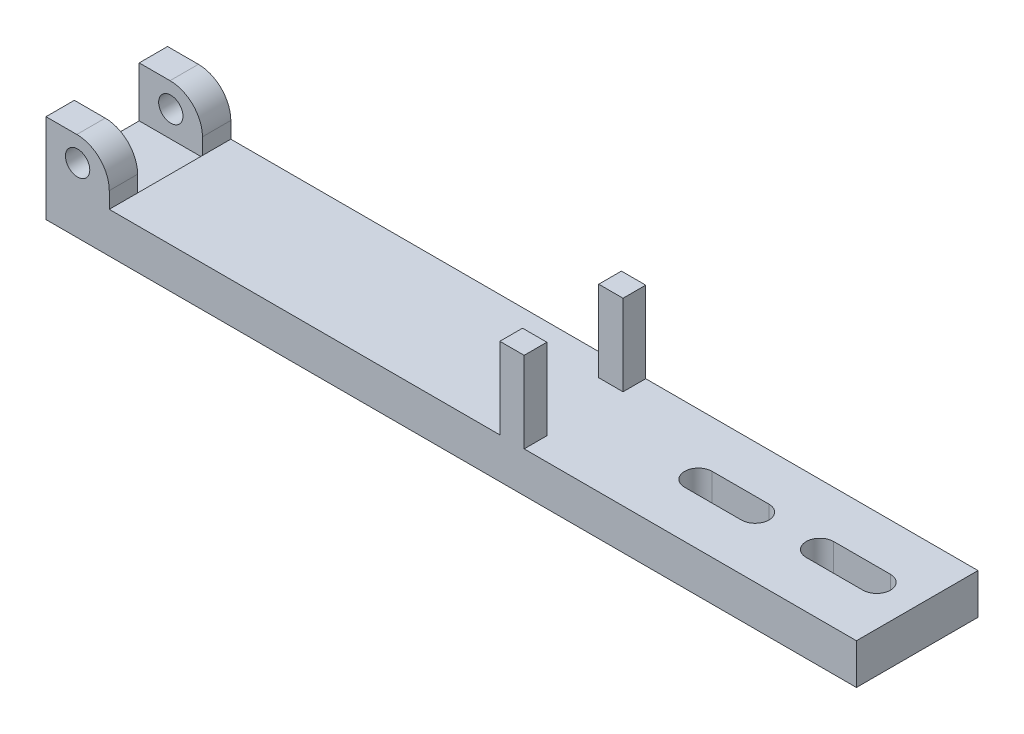
SolidWorks part; units mm, degrees
ref_plane "Ebene vorne" through (0, 0, 0) normal (0, 0, 1) x (1, 0, 0)
ref_plane "Ebene oben" through (0, 0, 0) normal (0, 1, 0) x (1, 0, 0)
ref_plane "Ebene rechts" through (0, 0, 0) normal (1, 0, 0) x (0, 0, -1)
sketch "Sketch1" plane through (0, 0, 0) normal (0, 1, 0) x (1, 0, 0)
  line L0 (-50, -7.5) -> (-50, 7.5)
  line L1 (-50, -7.5) -> (50, -7.5)
  line L2 (-50, 7.5) -> (50, 7.5)
  line L3 (50, -7.5) -> (50, 7.5)
  line L4 (-50, -7.5) -> (50, 7.5) construction
  line L5 (-50, 7.5) -> (50, -7.5) construction
  point P1 (0, 0)
  dimension "D1" = 15
  dimension "D2" = 100
extrude "Boss-Extrude1" add sketch "Sketch1" along normal blind 5
sketch "Sketch2" plane through (0, 5, 0) normal (0, 1, 0) x (1, 0, 0)
  line L0 (-50, -7.5) -> (50, -7.5) construction
  line L1 (-50, 7.5) -> (-42.1952, 7.5)
  line L2 (-50, 7.5) -> (-50, -7.5)
  line L3 (-50, -7.5) -> (-42.1952, -7.5)
  line L4 (-42.1952, 7.5) -> (-42.1952, -7.5)
extrude "Boss-Extrude2" add sketch "Sketch2" along normal blind 6
sketch "Sketch3" plane through (0, 0, 7.5) normal (0, 0, 1) x (1, 0, 0)
  line L1 (-42.1952, 8) -> (-50, 8) construction
  line L2 (-42.1952, 11) -> (-42.1952, 5) construction
  line L3 (-50, 11) -> (-50, 0) construction
  circle A0 centre (-46.0976, 8) radius 1.5
  dimension "D1" = 3
extrude "Cut-Extrude1" cut sketch "Sketch3" against normal up to surface (15 mm away) up to face at (-14.0651, 5.3333, -7.5)
fillet "Fillet1" radius 4 1 edges at (-42.1952, 11, 0)
sketch "Sketch4" plane through (0, 11, 0) normal (0, 1, 0) x (1, 0, 0)
  line L0 (-42.1952, 0) -> (-50, 0) construction
  line L1 (-42.1952, -7.5) -> (-42.1952, 7.5) construction
  line L2 (-50, 7.5) -> (-50, -7.5) construction
  line L3 (-50, -4) -> (-42.1952, -4)
  line L4 (-50, -4) -> (-50, 4)
  line L5 (-42.1952, -4) -> (-42.1952, 4)
  line L6 (-50, 4) -> (-42.1952, 4)
  line L7 (-50, -4) -> (-42.1952, 4) construction
  line L8 (-42.1952, -4) -> (-50, 4) construction
  point P7 (-46.0976, 0)
  dimension "D1" = 8
extrude "Cut-Extrude2" cut sketch "Sketch4" against normal blind 6.2
sketch "Sketch5" plane through (0, 0, 0) normal (0, -1, 0) x (1, 0, 0)
  line L0 (45, 0) -> (38, 0) construction
  line L1 (45, -1.7) -> (38, -1.7)
  line L2 (45, 1.7) -> (38, 1.7)
  line L3 (30, 0) -> (23, 0) construction
  line L4 (30, -1.7) -> (23, -1.7)
  line L5 (30, 1.7) -> (23, 1.7)
  line L7 (50, 7.5) -> (50, -7.5) construction
  arc A0 (45, -1.7) -> (45, 1.7) centre (45, 0) ccw
  arc A1 (38, 1.7) -> (38, -1.7) centre (38, 0) ccw
  arc A2 (30, -1.7) -> (30, 1.7) centre (30, 0) ccw
  arc A3 (23, 1.7) -> (23, -1.7) centre (23, 0) ccw
  point P3 (41.5, 0)
  point P8 (26.5, 0)
  dimension "D2" = 15
  dimension "^3,4" = 3.4
  dimension "D3" = 3.4
  dimension "D4" = 5
  dimension "D5" = 7
  dimension "D6" = 7
extrude "Cut-Extrude3" cut sketch "Sketch5" against normal up to surface (5 mm away) up to face at (-11.4635, 5, 0)
sketch "Sketch6" plane through (0, 5, 0) normal (0, 1, 0) x (1, 0, 0)
  line L0 (-50, 4) -> (-50, -4) construction
  line L1 (-26, 7.5) -> (-26, -7.5) construction
  line L2 (50, 7.5) -> (-42.1952, 7.5) construction
  line L3 (-42.1952, -7.5) -> (50, -7.5) construction
  circle A0 centre (-26, 0) radius 2.5
  point P10 (-26, 0)
  dimension "D1" = 5
  dimension "D2" = 24
extrude "Boss-Extrude3" [suppressed] add sketch "Sketch6" along normal blind 15
sketch "Sketch7" plane through (0, 5, 0) normal (0, 1, 0) x (1, 0, 0)
  line L0 (-42.1952, -7.5) -> (50, -7.5) construction
  line L1 (6, -7.5) -> (9, -7.5)
  line L2 (6, -7.5) -> (6, -4.7)
  line L3 (6, -4.7) -> (9, -4.7)
  line L4 (9, -7.5) -> (9, -4.7)
  line L5 (0, 0) -> (16.5077, 0) construction
  line L6 (50, -7.5) -> (50, 7.5) construction
  line L7 (9, 7.5) -> (9, 4.7)
  line L8 (6, 4.7) -> (9, 4.7)
  line L9 (6, 7.5) -> (6, 4.7)
  line L10 (6, 7.5) -> (9, 7.5)
  dimension "D1" = 2.8
  dimension "D2" = 3
  dimension "D3" = 41
extrude "Boss-Extrude4" add sketch "Sketch7" along normal blind 10
